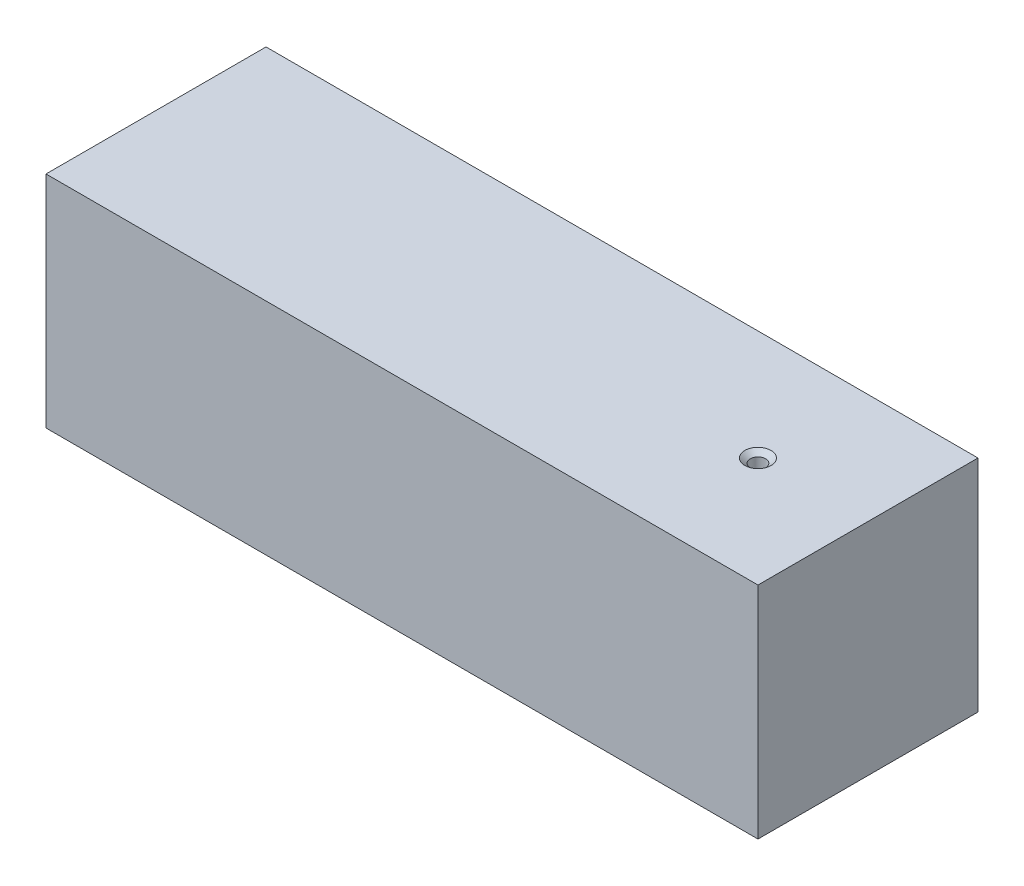
SolidWorks part; units mm, degrees
ref_plane "Front Plane" through (0, 0, 0) normal (0, 0, 1) x (1, 0, 0)
ref_plane "Top Plane" through (0, 0, 0) normal (0, 1, 0) x (1, 0, 0)
ref_plane "Right Plane" through (0, 0, 0) normal (1, 0, 0) x (0, 0, -1)
sketch "Sketch1" plane through (0, 0, 0) normal (0, 1, 0) x (1, 0, 0)
  line L1 (-41.095, -12.7) -> (41.095, -12.7)
  line L2 (-41.095, -12.7) -> (-41.095, 12.7)
  line L3 (-41.095, 12.7) -> (41.095, 12.7)
  line L4 (41.095, -12.7) -> (41.095, 12.7)
  line L5 (-41.095, -12.7) -> (41.095, 12.7) construction
  line L6 (-41.095, 12.7) -> (41.095, -12.7) construction
  point P0 (0, 0)
  dimension "D1" = 82.19
  dimension "D2" = 25.4
extrude "Boss-Extrude1" add sketch "Sketch1" along normal blind 25.4
hole_wizard "CSK for #0 Flat Head Machine Screw (100)1" positions "Sketch2" profile "Sketch3" countersink size "#0" standard "ANSI Inch" end condition through all
sketch "Sketch2" plane through (0, 25.4, 0) normal (0, 1, 0) x (1, 0, 0)
  line L0 (41.095, 12.7) -> (-41.095, 12.7) construction
  line L1 (41.095, -12.7) -> (41.095, 12.7) construction
  point P0 (28.395, 0)
  dimension "D1" = 12.7
  dimension "D2" = 12.7
sketch "Sketch3" plane through (28.395, 25.4, 0) normal (1, 0, 0) x (0, 0, 1)
  line L0 (0, 0) -> (0, 25.4)
  line L1 (0, 25.4) -> (0.889, 25.4)
  line L2 (0.889, 25.4) -> (0.889, 0.5222)
  line L3 (0.889, 0.5222) -> (1.5113, 0)
  line L5 (1.5113, 0) -> (0, 0)
  line L6 (-0.889, 0.5222) -> (-1.5113, 0) construction
  line L11 (0, -6.35) -> (0, 107.95) construction
  dimension "Thru Hole Dia." = 1.778
  dimension "Thru Hole Depth" = 25.4
  dimension "Near C'Sink Dia." = 3.0226
  dimension "Near C'Sink Angle" = 100
hole_wizard "#0-80 Tapped Hole1" positions "Sketch4" profile "Sketch5" tap size "#0-80" standard "ANSI Inch"
sketch "Sketch4" plane through (-41.095, 0, 0) normal (-1, 0, 0) x (0, 0, 1)
  line L0 (0, 0) -> (0, 25.4) construction
  line L1 (-12.7, 0) -> (12.7, 0) construction
  line L2 (-12.7, 25.4) -> (12.7, 25.4) construction
  line L4 (-12.7, 12.7) -> (12.7, 12.7) construction
  line L5 (-12.7, 25.4) -> (-12.7, 0) construction
  line L6 (12.7, 25.4) -> (12.7, 0) construction
  point P0 (0, 12.7)
  point P20 (0, 12.7)
sketch "Sketch5" plane through (-41.095, 12.7, 0) normal (0, 1, 0) x (0, 0, 1)
  line L0 (0, 0) -> (0, 20.3579)
  line L1 (0, 20.3579) -> (0.5956, 20)
  line L2 (0.5956, 20) -> (0.5956, 0.7683)
  line L3 (0.5956, 0.7683) -> (1.5113, 0)
  line L5 (1.5113, 0) -> (0, 0)
  line L6 (-0.5956, 0.7683) -> (-1.5113, 0) construction
  line L10 (0, 20.3579) -> (-0.5956, 20) construction
  line L11 (0, -6.35) -> (0, 107.95) construction
  dimension "Tap Drill Dia." = 1.1913
  dimension "Tap Drill Depth" = 20
  dimension "Near C'Sink Dia." = 3.0226
  dimension "Near C'Sink Angle" = 100
  dimension "Drill Angle" = 118
cosmetic thread "Hole Thread2"
